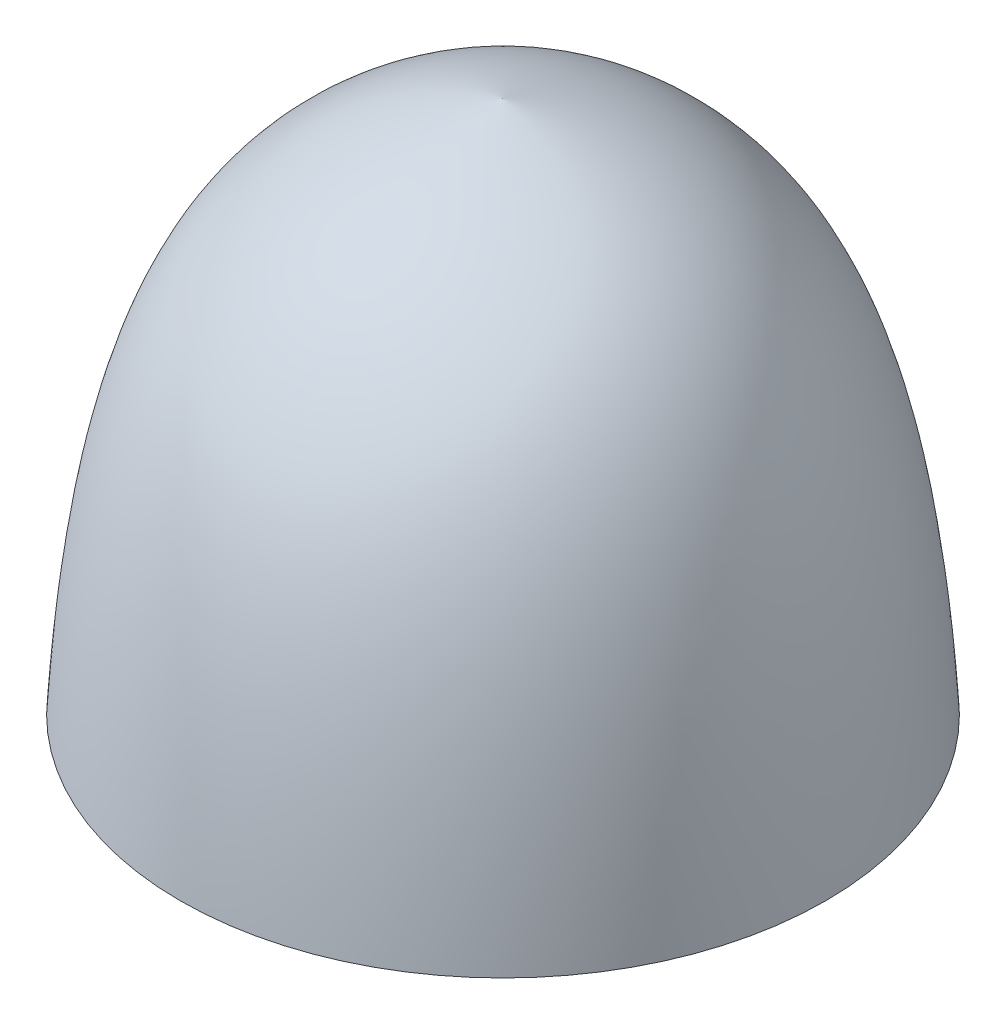
SolidWorks part; units mm, degrees
ref_plane "Front Plane" through (0, 0, 0) normal (0, 0, 1) x (1, 0, 0)
ref_plane "Top Plane" through (0, 0, 0) normal (0, 1, 0) x (1, 0, 0)
ref_plane "Right Plane" through (0, 0, 0) normal (1, 0, 0) x (0, 0, -1)
sketch "Sketch1" plane through (0, 0, 0) normal (0, 0, 1) x (1, 0, 0)
  line L0 (0, 19.05) -> (0, 29.213) construction
  line L1 (0, 0) -> (12.7, 0)
  line L2 (0, 0) -> (0, 19.05)
  line L5 (12.7, 0) -> (17.6798, 0) construction
  line L6 (0, 19.05) -> (0, 29.213)
  line L7 (12.7, 0) -> (17.6798, 0)
  spline S0 degree 3 poles (17.6798, 0) (16.4856, 19.4435) (12.1252, 26.4924) (0, 29.213) knots 0 0 0 0 1 1 1 1
  dimension "D3" = 37.4654
  dimension "D1" = 12.7
  dimension "D2" = 19.05
  dimension "D4" = 34.1463
revolve "Revolve2" add sketch "Sketch1" angle 360 about L2
sketch "Sketch4" plane through (0, 0, 0) normal (0, -1, 0) x (1, 0, 0)
  circle A0 centre (0, 0) radius 12.7
  dimension "D1" = 25.4
extrude "Cut-Extrude1" cut sketch "Sketch4" against normal blind 19.05
ref_axis "Axis2" through (0, 0, 0) along (0, 1, 0)
